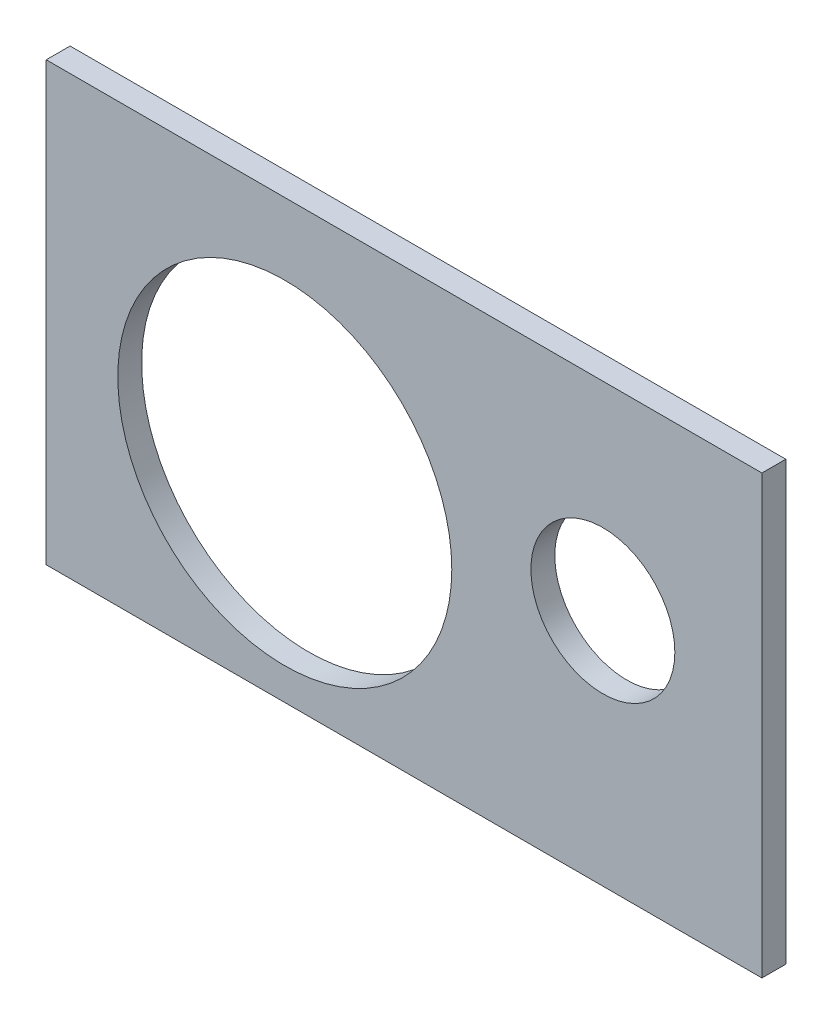
SolidWorks part; units mm, degrees
ref_plane "Front Plane" through (0, 0, 0) normal (0, 0, 1) x (1, 0, 0)
ref_plane "Top Plane" through (0, 0, 0) normal (0, 1, 0) x (1, 0, 0)
ref_plane "Right Plane" through (0, 0, 0) normal (1, 0, 0) x (0, 0, -1)
sketch "Sketch1" plane through (0, 0, 0) normal (0, 0, 1) x (1, 0, 0)
  line L1 (0, 0) -> (180, 0)
  line L2 (0, 0) -> (0, 110)
  line L3 (0, 110) -> (180, 110)
  line L4 (180, 0) -> (180, 110)
  circle A0 centre (60, 50) radius 42
  circle A1 centre (140, 60) radius 18.1
extrude "Boss-Extrude1" add sketch "Sketch1" along normal blind 6
sketch "Sketch2" plane through (0, 0, 0) normal (0, 0, 1) x (1, 0, 0)
  point P0 (60, 50)
